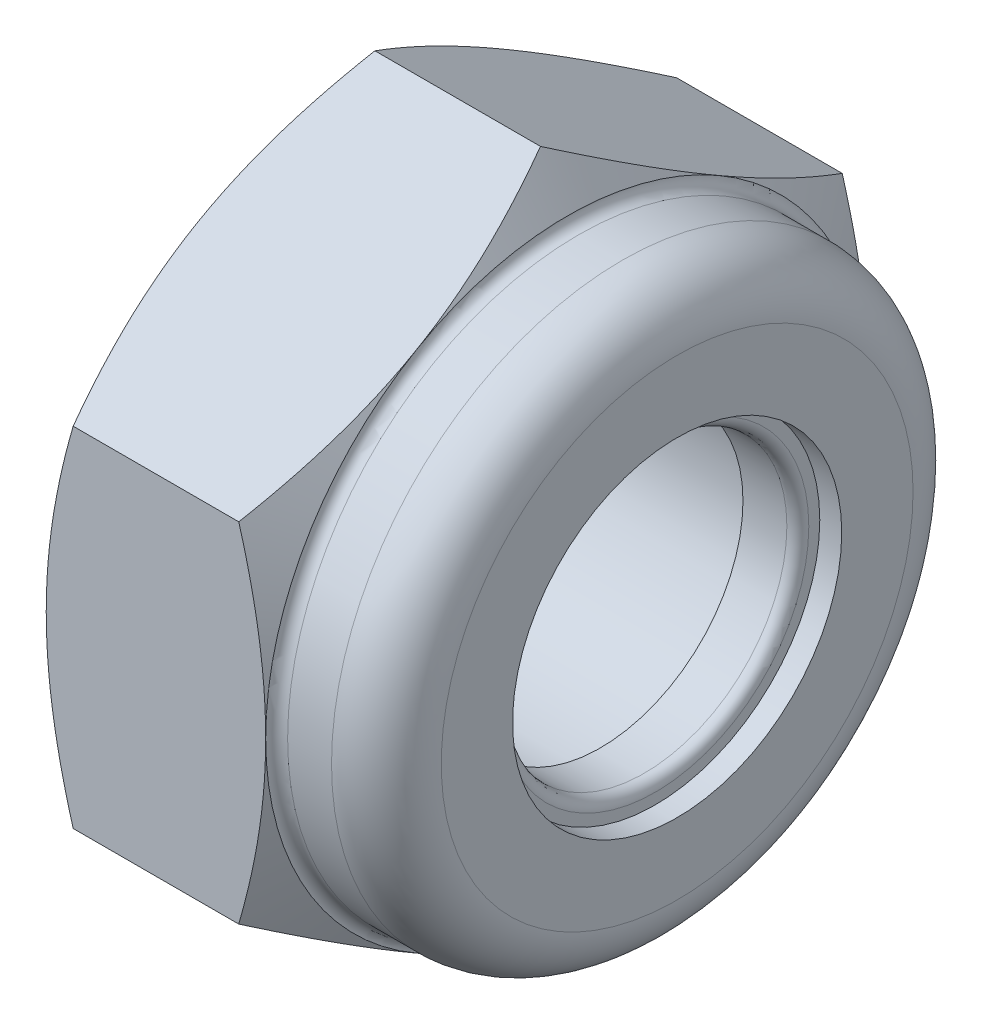
SolidWorks part; units mm, degrees
ref_plane "前视基准面" through (0, 0, 0) normal (0, 0, 1) x (1, 0, 0)
ref_plane "上视基准面" through (0, 0, 0) normal (0, 1, 0) x (1, 0, 0)
ref_plane "右视基准面" through (0, 0, 0) normal (1, 0, 0) x (0, 0, -1)
sketch "草图1" plane through (0, 0, 0) normal (1, 0, 0) x (0, 0, -1)
  line L0 (0, 3.1754) -> (-2.75, 1.5877)
  line L1 (-2.75, 1.5877) -> (-2.75, -1.5877)
  line L2 (-2.75, -1.5877) -> (0, -3.1754)
  line L3 (0, -3.1754) -> (2.75, -1.5877)
  line L4 (2.75, -1.5877) -> (2.75, 1.5877)
  line L5 (2.75, 1.5877) -> (0, 3.1754)
  circle A0 centre (0, 0) radius 1.5
  circle A1 centre (0, 0) radius 3.1754 construction
  dimension "D1" = 3
  dimension "D2" = 5.5
extrude "凸台-拉伸1" add sketch "草图1" along normal blind 2
cosmetic thread "装饰螺纹线1" parameters "D2"=4
sketch "草图2" plane through (0, 0, 0) normal (-1, 0, 0) x (0, 0, 1)
  circle A0 centre (0, 0) radius 2.75
extrude "切除-拉伸1" cut sketch "草图2" against normal blind 2 draft 60 flip side to cut
sketch "草图3" plane through (2, 0, 0) normal (1, 0, 0) x (0, 0, -1)
  circle A0 centre (0, 0) radius 2.75
extrude "切除-拉伸2" cut sketch "草图3" against normal blind 2 draft 60 flip side to cut
sketch "草图4" plane through (2, 0, 0) normal (1, 0, 0) x (0, 0, -1)
  circle A0 centre (0, 0) radius 1.5
  circle A1 centre (0, 0) radius 2.65
  arc A2 (1.375, -2.3816) -> (2.75, 0) centre (0, 0) ccw construction
  dimension "D1" = 3
  dimension "D2" = 0.1
extrude "凸台-拉伸2" add sketch "草图4" along normal blind 1
fillet "圆角1" radius 0.1 1 edges at (2, 0, -2.65)
fillet "圆角2" radius 0.5 1 edges at (3, 0, -2.65)
sketch "草图5" plane through (3, 0, 0) normal (1, 0, 0) x (0, 0, -1)
  circle A0 centre (0, 0) radius 1.3
  circle A1 centre (0, 0) radius 1.7
  circle A2 centre (0, 0) radius 1.5 construction
  dimension "D1" = 0.2
  dimension "D2" = 0.2
extrude "凸台-拉伸3" add sketch "草图5" against normal blind 0.5 from offset 0.2 offset against normal yes
fillet "圆角3" radius 0.1 1 edges at (2.8, 0, -1.3)
